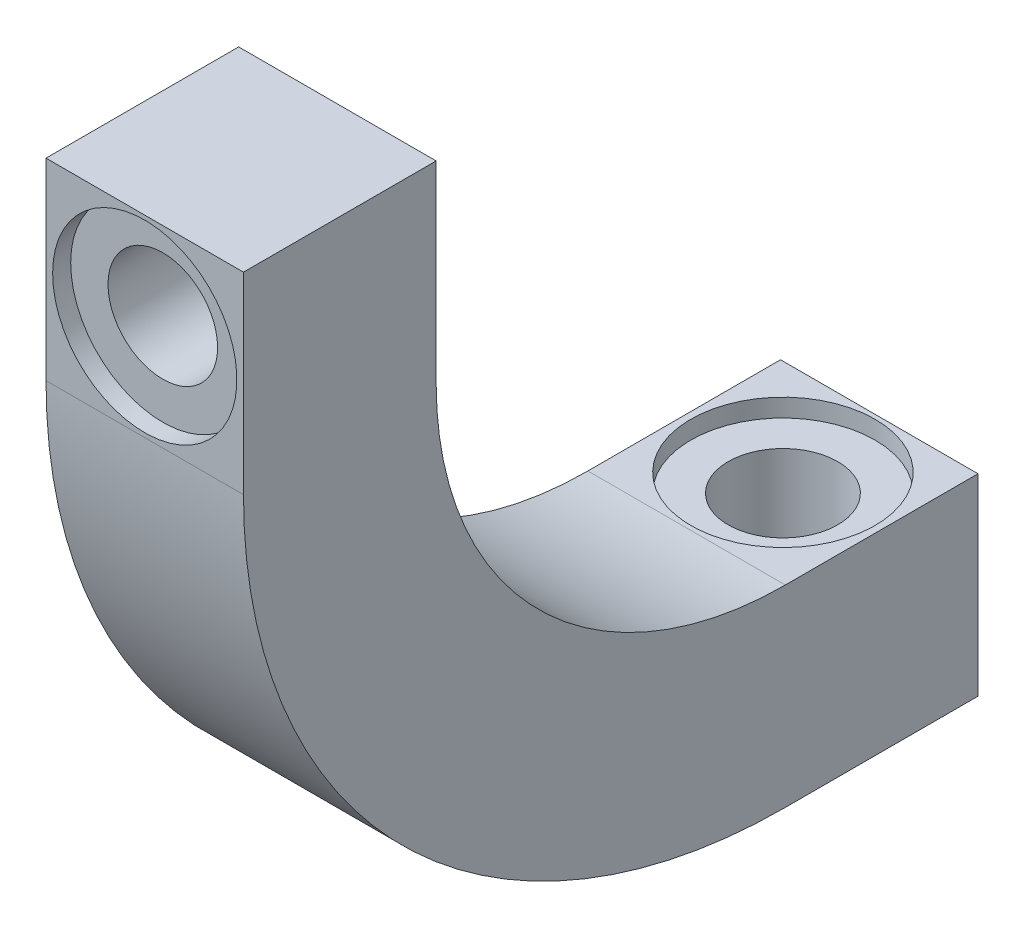
SolidWorks part; units mm, degrees
ref_plane "Front Plane" through (0, 0, 0) normal (0, 0, 1) x (1, 0, 0)
ref_plane "Top Plane" through (0, 0, 0) normal (0, 1, 0) x (1, 0, 0)
ref_plane "Right Plane" through (0, 0, 0) normal (1, 0, 0) x (0, 0, -1)
ref_axis "Z" through (0, 0, 22.75) along (0, 0, -1)
sketch "Sketch4" plane through (0, 0, 0) normal (0, 0, 1) x (1, 0, 0)
  circle A0 centre (0, 0) radius 17.5 construction
  dimension "D1" = 35
sketch "Sketch5" plane through (0, 0, 0) normal (1, 0, 0) x (0, 0, -1)
  line L0 (-18.5, 4) -> (-18.5, 0)
  line L1 (-18.5, 0) -> (-18.5, -4)
  line L2 (-26.5, -4) -> (-26.5, 4)
  line L6 (-26.5, 4) -> (-18.5, 4)
  line L12 (-22.75, 0) -> (-13.0351, 0) construction
  line L13 (0, 0) -> (-14.9091, -14.9091) construction
  line L14 (0, 0) -> (7.0065, 0) construction
  line L15 (0, -18.5) -> (-4, -18.5)
  line L16 (4, -18.5) -> (0, -18.5)
  line L17 (-4, -26.5) -> (4, -26.5)
  line L18 (4, -26.5) -> (4, -18.5)
  circle A0 centre (0, 0) radius 14 construction
  arc A1 (-18.5, -4) -> (-4, -18.5) centre (-4, -4) ccw
  arc A2 (-26.5, -4) -> (-4, -26.5) centre (-4, -4) ccw
  point P2 (9.4307, -21)
  point P4 (0, -2.1363)
  dimension "D1" = 28
  dimension "D4" = 4
  dimension "D2" = 45
  dimension "D3" = 8
  dimension "D5" = 18.5
sketch "Sketch6" plane through (0, 0, 0) normal (0, 1, 0) x (1, 0, 0)
  circle A0 centre (0, 0) radius 17.5 construction
  dimension "D1" = 35
extrude "Boss-Extrude1" add sketch "Sketch5" along normal blind 4.1 and the other way blind 4.1
sketch "Sketch7" plane through (0, 0, 0) normal (0, 0, 1) x (1, 0, 0)
  circle A0 centre (0, 0) radius 1.75
  dimension "D1" = 3.5
extrude "Cut-Extrude1" cut sketch "Sketch7" along normal through all
sketch "Sketch8" plane through (0, 0, 0) normal (0, 1, 0) x (1, 0, 0)
  circle A0 centre (0, 0) radius 1.75
  dimension "D1" = 3.5
extrude "Cut-Extrude2" cut sketch "Sketch8" against normal through all
ref_axis "Y" through (0, -9.3489, 0) along (0, -1, 0)
sketch "Sketch11" plane through (0, -18.5, 0) normal (0, -1, 0) x (1, 0, 0)
  circle A0 centre (0, 0) radius 2.275
  point P2 (-13.2782, 2.4361)
  dimension "D1" = 4.55
extrude "Cut-Extrude6" cut sketch "Sketch11" along normal blind 6
sketch "Sketch12" plane through (0, 0, 26.5) normal (0, 0, 1) x (1, 0, 0)
  circle A0 centre (0, 0) radius 2.275
  point P2 (-9.7185, 1.8171)
  point P4 (0, 0)
  dimension "D1" = 4.55
extrude "Cut-Extrude7" cut sketch "Sketch12" against normal blind 6
sketch "Sketch13" plane through (0, -18.5, 0) normal (0, -1, 0) x (1, 0, 0)
  circle A0 centre (0, 0) radius 3.825
  point P2 (-7.7371, 1.4245)
  dimension "D1" = 7.65
extrude "Cut-Extrude8" cut sketch "Sketch13" along normal blind 0.75
sketch "Sketch14" plane through (0, 0, 26.5) normal (0, 0, -1) x (1, 0, 0)
  circle A0 centre (0, 0) radius 3.825
  point P2 (-7.7371, 1.4245)
  point P4 (-8.3097, 0.2916)
  dimension "D1" = 7.65
extrude "Cut-Extrude10" cut sketch "Sketch14" along normal blind 0.75
ref_plane "Plane1" through (0, -18.5, 0) normal (0, 1, 0) x (1, 0, 0)
ref_axis "CX" through (0, -18.5, 4.4) along (0, 0, -1)
ref_plane "Plane2" through (0, 0, 0) normal (0, 0, -1) x (0, 1, 0)
ref_plane "Plane3" through (0, 0, 0) normal (1, 0, 0) x (0, 0, -1)
ref_axis "CZ" through (0, -8.7018, 0) along (0, -1, 0)
ref_axis "CY" through (-0.6471, -18.5, 0) along (1, 0, 0)
ref_point "CO"
equation "\"rbracket-width\"= \"L2Thickness\" + 0.2"
equation "\"EyeCaptureRadius\"= ( \"EyeDiameter\" + \"EyeClearance\" ) / 2"
equation "\"rbracket_planetocenterline_dist\"= \"BasePlaneDistance\""
equation "\"EyeDiameter\" = 35"
equation "\"BasePlaneDistance\" = \"EyeDiameter\"/2+19.84"
equation "\"EyeClearance\" = 2"
equation "\"D1@Sketch4\"=\"EyeDiameter\""
equation "\"D1@Sketch6\"=\"EyeDiameter\""
equation "\"D1@Boss-Extrude1\"=\"rbracket-width\"/2"
equation "\"D2@Boss-Extrude1\"=\"rbracket-width\"/2"
equation "\"L2Thickness\" = 8"
equation "\"D3@Sketch5\"=\"L2Thickness\""
equation "\"D5@Sketch5\"=(\"EyeDiameter\"+\"EyeClearance\")/2"
equation "\"BearingThickness\"= 6"
equation "\"BearingOD\"=4.5"
equation "\"OuterBearingProudDistance\"= 0"
equation "\"D1@Cut-Extrude7\"=\"BearingThickness\"-\"OuterBearingProudDistance\""
equation "\"D1@Cut-Extrude6\"=\"BearingThickness\" - \"OuterBearingProudDistance\""
equation "\"D1@Sketch11\"=\"BearingOD\" + \"PrinterFilamentThickness\"*\"ApplyPrinterOffset\"/2"
equation "\"D1@Sketch12\"= \"BearingOD\" + \"PrinterFilamentThickness\" *\"ApplyPrinterOffset\" / 2"
equation "\"FlangeOD\"=7.5"
equation "\"FlangeThickness\"= 0.75"
equation "\"D1@Sketch14\"=\"FlangeOD\" + \"PrinterFilamentThickness\"*1.5 * \"ApplyPrinterOffset\""
equation "\"D1@Cut-Extrude10\"=\"FlangeThickness\""
equation "\"PrinterFilamentThickness\"= 0.1'For setting distances for things like pressfits"
equation "\"ApplyPrinterOffset\"= 1'Set to 0 for line-to-line. Set to 1 for applying guestimate dimensions to make the printer produce good parts"
equation "\"D1@Sketch13\"=\"FlangeOD\" + \"PrinterFilamentThickness\"*1.5 * \"ApplyPrinterOffset\""
